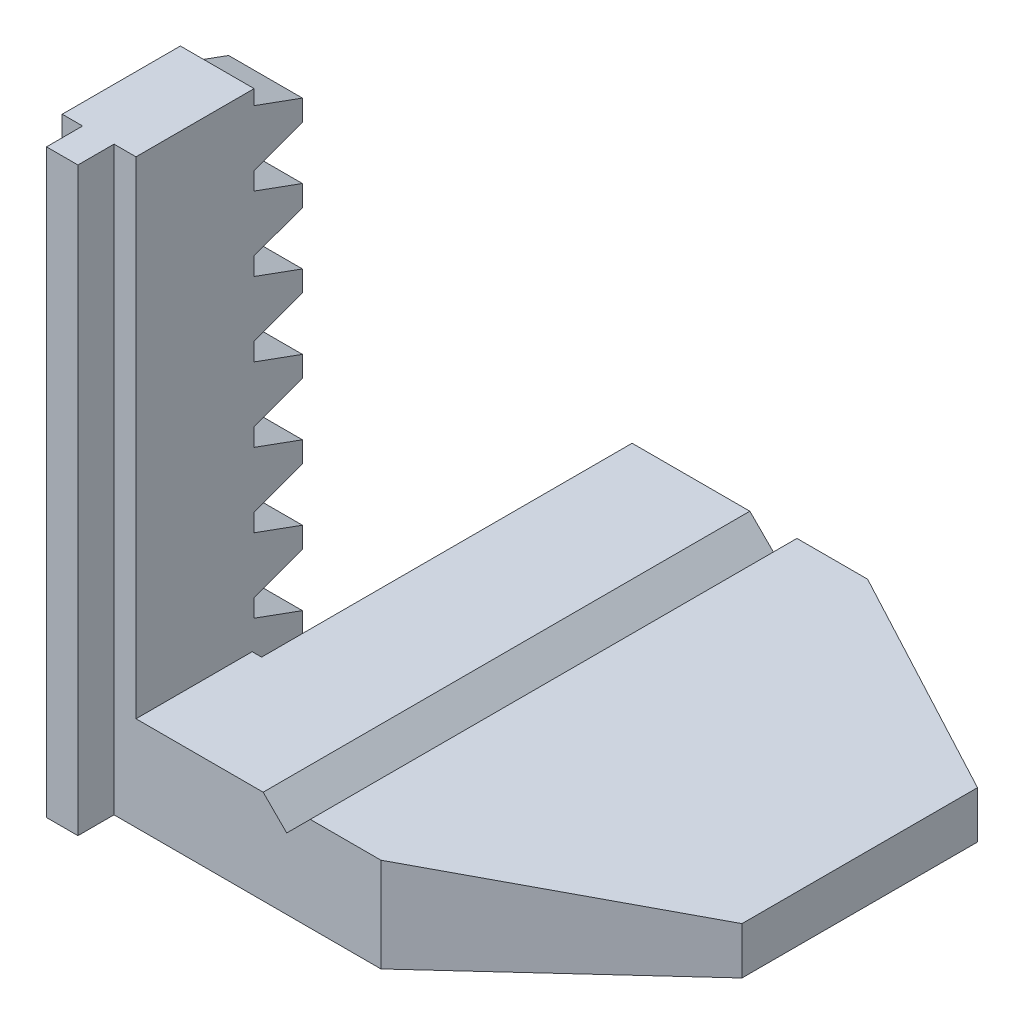
SolidWorks part; units mm, degrees
ref_plane "Front Plane" through (0, 0, 0) normal (0, 0, 1) x (1, 0, 0)
ref_plane "Top Plane" through (0, 0, 0) normal (0, 1, 0) x (1, 0, 0)
ref_plane "Right Plane" through (0, 0, 0) normal (1, 0, 0) x (0, 0, -1)
ref_plane "Plane1" through (209.7, 0, 0) normal (1, 0, 0) x (0, 0, -1)
ref_plane "Plane2" through (211, 0, 0) normal (1, 0, 0) x (0, 0, -1)
ref_plane "Plane3" through (214.4, 0, 0) normal (1, 0, 0) x (0, 0, -1)
ref_plane "Plane4" through (215, 0, 0) normal (1, 0, 0) x (0, 0, -1)
sketch "Sketch1" plane through (209.7, 0, 0) normal (1, 0, 0) x (0, 0, -1)
  line L0 (-318, -6) -> (-318, 31)
  line L1 (-318, 31) -> (-310.475, 31)
  line L2 (-310.475, 31) -> (-310.475, 30.0599)
  line L3 (-310.475, 30.0599) -> (-307.4, 28.9407)
  line L4 (-307.4, 28.9407) -> (-307.4, 27.608)
  line L5 (-307.4, 27.608) -> (-310.475, 26.4888)
  line L6 (-310.475, 26.4888) -> (-310.475, 25.3475)
  line L7 (-310.475, 25.3475) -> (-307.4, 24.2283)
  line L8 (-307.4, 24.2283) -> (-307.4, 22.8956)
  line L9 (-307.4, 22.8956) -> (-310.475, 21.7764)
  line L10 (-310.475, 21.7764) -> (-310.475, 20.6351)
  line L11 (-310.475, 20.6351) -> (-307.4, 19.5159)
  line L12 (-307.4, 19.5159) -> (-307.4, 18.1832)
  line L13 (-307.4, 18.1832) -> (-310.475, 17.064)
  line L14 (-310.475, 17.064) -> (-310.475, 15.9227)
  line L15 (-310.475, 15.9227) -> (-307.4, 14.8035)
  line L16 (-307.4, 14.8035) -> (-307.4, 13.4708)
  line L17 (-307.4, 13.4708) -> (-310.475, 12.3516)
  line L18 (-310.475, 12.3516) -> (-310.475, 11.2103)
  line L19 (-310.475, 11.2103) -> (-307.4, 10.0911)
  line L20 (-307.4, 10.0911) -> (-307.4, 8.7584)
  line L21 (-307.4, 8.7584) -> (-310.475, 7.6392)
  line L22 (-310.475, 7.6392) -> (-310.475, 6.4979)
  line L23 (-310.475, 6.4979) -> (-307.4, 5.3787)
  line L24 (-307.4, 5.3787) -> (-307.4, 4.0461)
  line L25 (-307.4, 4.0461) -> (-310.475, 2.9268)
  line L26 (-310.475, 2.9268) -> (-310.475, 1.7855)
  line L27 (-310.475, 1.7855) -> (-307.4, 0.6663)
  line L28 (-307.4, 0.6663) -> (-307.4, -0.6663)
  line L29 (-307.4, -0.6663) -> (-310.475, -1.7855)
  line L30 (-310.475, -1.7855) -> (-310.475, -2.9268)
  line L31 (-310.475, -2.9268) -> (-307.4, -4.0461)
  line L32 (-307.4, -4.0461) -> (-307.4, -5.3787)
  line L33 (-307.4, -5.3787) -> (-309.1069, -6)
  line L34 (-309.1069, -6) -> (-318, -6)
extrude "Boss-Extrude1" add sketch "Sketch1" along normal blind 4.7
sketch "Sketch2" plane through (211, 0, 0) normal (1, 0, 0) x (0, 0, -1)
  line L1 (-320.3, -6) -> (-317.9, -6)
  line L2 (-320.3, -6) -> (-320.3, 31)
  line L3 (-320.3, 31) -> (-317.9, 31)
  line L4 (-317.9, -6) -> (-317.9, 31)
extrude "Boss-Extrude2" add sketch "Sketch2" along normal blind 2
sketch "Sketch3" plane through (214.4, 0, 0) normal (1, 0, 0) x (0, 0, -1)
  line L1 (-318, -6) -> (-310.6, -6)
  line L2 (-318, -6) -> (-318, 0)
  line L3 (-318, 0) -> (-310.6, 0)
  line L4 (-310.6, -6) -> (-310.6, 0)
extrude "Boss-Extrude3" add sketch "Sketch3" along normal blind 0.8
sketch "Sketch4" plane through (215, 0, 0) normal (1, 0, 0) x (0, 0, -1)
  line L1 (-318, -6) -> (-287, -6)
  line L2 (-318, -6) -> (-318, 0)
  line L3 (-318, 0) -> (-287, 0)
  line L4 (-287, -6) -> (-287, 0)
extrude "Boss-Extrude4" add sketch "Sketch4" along normal blind 30
sketch "Sketch5" plane through (0, 0, 0) normal (0, 1, 0) x (1, 0, 0)
  line L0 (228.125, -319) -> (246.5, -309.2)
  line L1 (246.5, -309.2) -> (246.5, -319)
  line L2 (246.5, -319) -> (228.125, -319)
  line L3 (228.125, -286) -> (246.5, -295.8)
  line L4 (246.5, -295.8) -> (246.5, -286)
  line L5 (246.5, -286) -> (228.125, -286)
extrude "Cut-Extrude1" cut sketch "Sketch5" along normal mid plane 13
sketch "Sketch6" plane through (0, 0, 0) normal (0, 0, 1) x (1, 0, 0)
  line L0 (227.5, -6.5) -> (246.5, -2.7)
  line L1 (246.5, -2.7) -> (246.5, -6.5)
  line L2 (246.5, -6.5) -> (227.5, -6.5)
extrude "Cut-Extrude2" cut sketch "Sketch6" along normal through all
sketch "Sketch7" plane through (0, 0, 0) normal (0, 0, 1) x (1, 0, 0)
  line L0 (222, 0.5) -> (226, 0.5)
  line L1 (226, 0.5) -> (224, -1.5)
  line L2 (224, -1.5) -> (222, 0.5)
extrude "Cut-Extrude3" cut sketch "Sketch7" along normal through all
